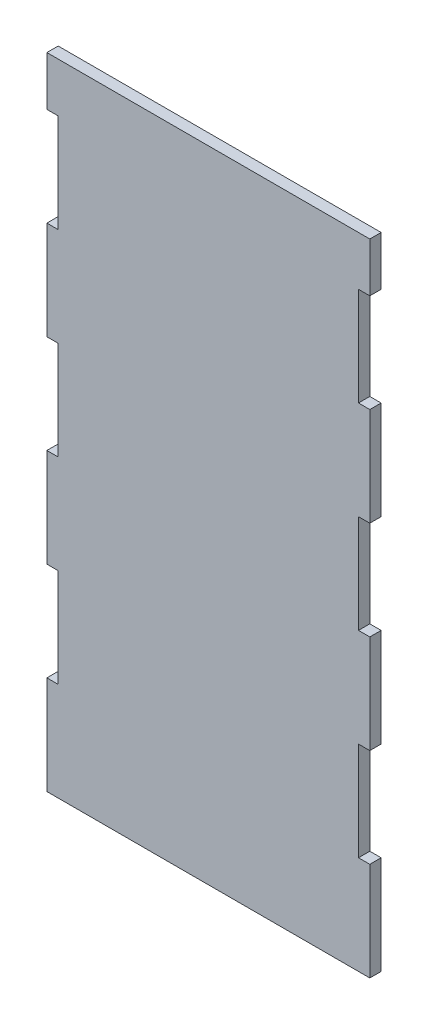
SolidWorks part; units mm, degrees
ref_plane "Front Plane" through (0, 0, 0) normal (0, 0, 1) x (1, 0, 0)
ref_plane "Top Plane" through (0, 0, 0) normal (0, 1, 0) x (1, 0, 0)
ref_plane "Right Plane" through (0, 0, 0) normal (1, 0, 0) x (0, 0, -1)
sketch "Sketch1" plane through (0, 0, 0) normal (0, 0, 1) x (1, 0, 0)
  line L1 (-41.656, 82.55) -> (41.656, 82.55)
  line L2 (-41.656, 82.55) -> (-41.656, -82.55)
  line L3 (-41.656, -82.55) -> (41.656, -82.55)
  line L4 (41.656, 82.55) -> (41.656, -82.55)
  point P4 (0, 82.55)
  point P6 (-41.656, 0)
  dimension "D1" = 83.312
  dimension "D2" = 165.1
extrude "Boss-Extrude1" add sketch "Sketch1" along normal mid plane 2.921
sketch "Sketch2" plane through (0, 0, 1.4605) normal (0, 0, 1) x (1, 0, 0)
  line L0 (-38.735, -82.55) -> (38.735, -82.55)
  line L1 (-41.656, 82.55) -> (41.656, 82.55)
  line L2 (-41.656, 82.55) -> (-41.656, -82.55)
  line L3 (-41.656, -82.55) -> (-38.735, -82.55)
  line L4 (41.656, 82.55) -> (41.656, -82.55)
  line L5 (38.735, -82.55) -> (41.656, -82.55)
  line L6 (-41.656, 82.55) -> (-38.735, 82.55)
  line L7 (-41.656, 82.55) -> (-41.656, -82.55)
  line L8 (-41.656, -82.55) -> (-38.735, -82.55)
  line L9 (-38.735, 82.55) -> (-38.735, -82.55)
  line L10 (41.656, 82.55) -> (38.735, 82.55)
  line L11 (41.656, 82.55) -> (41.656, -82.55)
  line L12 (41.656, -82.55) -> (38.735, -82.55)
  line L13 (38.735, 82.55) -> (38.735, -82.55)
  line L14 (-41.656, -57.15) -> (-38.735, -57.15)
  line L15 (38.735, -57.15) -> (41.656, -57.15)
  line L16 (-41.656, -31.75) -> (-38.735, -31.75)
  line L17 (38.735, -31.75) -> (41.656, -31.75)
  line L18 (-41.656, -6.35) -> (-38.735, -6.35)
  line L19 (38.735, -6.35) -> (41.656, -6.35)
  line L20 (-41.656, 19.05) -> (-38.735, 19.05)
  line L21 (38.735, 19.05) -> (41.656, 19.05)
  line L22 (-41.656, 44.45) -> (-38.735, 44.45)
  line L23 (38.735, 44.45) -> (41.656, 44.45)
  line L24 (-41.656, 69.85) -> (-38.735, 69.85)
  line L25 (38.735, 69.85) -> (41.656, 69.85)
  line L26 (-41.656, -82.55) -> (-41.656, -57.15) construction
  dimension "D1" = 2.921
  dimension "D2" = 2.921
  dimension "D4" = 25.4
  dimension "D5" = 2.921
  dimension "D6" = 2.921
  dimension "D3" = 7
extrude "Cut-Extrude1" cut sketch "Sketch2" against normal blind 2.921 contours L24 L7 L22 L9 | L20 L7 L18 L9 | L16 L7 L14 L9 | L17 L13 L15 L11 | L21 L13 L19 L11 | L25 L13 L23 L11 region at (-40.1955, -44.45, 1.4605) region at (40.1955, -44.45, 1.4605) region at (-40.1955, 6.35, 1.4605) region at (40.1955, 6.35, 1.4605) region at (-40.1955, 57.15, 1.4605) region at (40.1955, 57.15, 1.4605)
